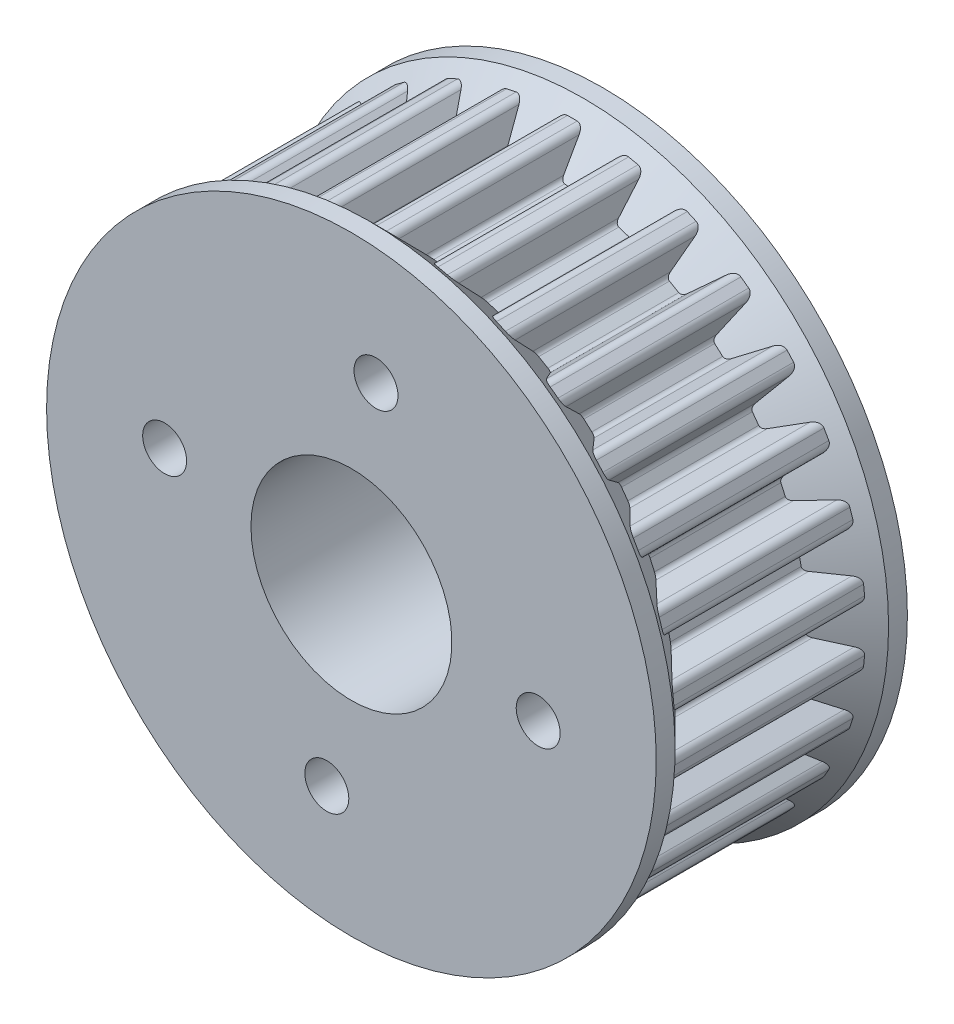
SolidWorks part; units mm, degrees
ref_plane "Plan de face" through (0, 0, 0) normal (0, 0, 1) x (1, 0, 0)
ref_plane "Plan de dessus" through (0, 0, 0) normal (0, 1, 0) x (1, 0, 0)
ref_plane "Plan de droite" through (0, 0, 0) normal (1, 0, 0) x (0, 0, -1)
sketch "Esquisse1" plane through (0, 0, 0) normal (0, 0, 1) x (1, 0, 0)
  line L0 (0, 0) -> (0, 23.875) construction
  line L1 (0, 0) -> (4.9639, 23.3533) construction
  line L2 (0, 0) -> (2.4956, 23.7442) construction
  line L3 (0.3858, 23.3597) -> (0, 23.3597)
  line L4 (0.9653, 22.915) -> (1.4252, 21.1988)
  line L5 (1.7697, 20.9045) -> (2.6152, 20.8157)
  line L6 (3.8201, 22.6149) -> (3.0135, 21.0319)
  line L7 (4.4794, 22.9294) -> (4.8568, 22.8492)
  line L8 (5.2341, 22.769) -> (4.8568, 22.8492)
  line L9 (5.7085, 22.2135) -> (5.8015, 20.4393)
  line L10 (6.0773, 20.0798) -> (6.8859, 19.8171)
  line L11 (8.4385, 21.3265) -> (7.3204, 19.9457)
  line L12 (9.1488, 21.497) -> (9.5012, 21.3401)
  line L13 (9.8537, 21.1832) -> (9.5012, 21.3401)
  line L14 (10.2022, 20.5412) -> (9.9243, 18.7864)
  line L15 (10.1194, 18.3774) -> (10.8556, 17.9523)
  line L16 (12.6881, 19.106) -> (11.3074, 17.9879)
  line L17 (13.4184, 19.1251) -> (13.7305, 18.8984)
  line L18 (14.0426, 18.6716) -> (13.7305, 18.8984)
  line L19 (14.25, 17.9712) -> (13.6133, 16.3125)
  line L20 (13.7191, 15.8719) -> (14.3509, 15.303)
  line L21 (16.3832, 16.0505) -> (14.8002, 15.2439)
  line L22 (17.1015, 15.9174) -> (17.3596, 15.6307)
  line L23 (17.6178, 15.344) -> (17.3596, 15.6307)
  line L24 (17.6751, 14.6157) -> (16.7074, 13.1257)
  line L25 (16.7193, 12.6727) -> (17.219, 11.9849)
  line L26 (19.3623, 12.2935) -> (17.6461, 11.8336)
  line L27 (20.0372, 12.0139) -> (20.2301, 11.6798)
  line L28 (20.423, 11.3458) -> (20.2301, 11.6798)
  line L29 (20.3276, 10.6215) -> (19.0713, 9.3652)
  line L30 (18.9887, 8.9196) -> (19.3345, 8.143)
  line L31 (21.4951, 7.9992) -> (19.7209, 7.9062)
  line L32 (22.0972, 7.5854) -> (22.2164, 7.2185)
  line L33 (22.3356, 6.8517) -> (22.2164, 7.2185)
  line L34 (22.0917, 6.163) -> (20.6017, 5.1954)
  line L35 (20.4283, 4.7767) -> (20.605, 3.9451)
  line L36 (22.6885, 3.3553) -> (20.9337, 3.6332)
  line L37 (23.1914, 2.8254) -> (23.2317, 2.4418)
  line L38 (23.272, 2.0581) -> (23.2317, 2.4418)
  line L39 (22.8903, 1.4352) -> (21.2317, 0.7985)
  line L40 (20.975, 0.4251) -> (20.975, -0.4251)
  line L41 (22.8903, -1.4352) -> (21.2317, -0.7985)
  line L42 (23.272, -2.0581) -> (23.2317, -2.4418)
  line L43 (23.1914, -2.8254) -> (23.2317, -2.4418)
  line L44 (22.6885, -3.3553) -> (20.9337, -3.6332)
  line L45 (20.605, -3.9451) -> (20.4283, -4.7767)
  line L46 (22.0917, -6.163) -> (20.6017, -5.1954)
  line L47 (22.3356, -6.8517) -> (22.2164, -7.2185)
  line L48 (22.0972, -7.5854) -> (22.2164, -7.2185)
  line L49 (21.4951, -7.9992) -> (19.7209, -7.9062)
  line L50 (19.3345, -8.143) -> (18.9887, -8.9196)
  line L51 (20.3276, -10.6215) -> (19.0713, -9.3652)
  line L52 (20.423, -11.3458) -> (20.2301, -11.6798)
  line L53 (20.0372, -12.0139) -> (20.2301, -11.6798)
  line L54 (19.3623, -12.2935) -> (17.6461, -11.8336)
  line L55 (17.219, -11.9849) -> (16.7193, -12.6727)
  line L56 (17.6751, -14.6157) -> (16.7074, -13.1257)
  line L57 (17.6178, -15.344) -> (17.3596, -15.6307)
  line L58 (17.1015, -15.9174) -> (17.3596, -15.6307)
  line L59 (16.3832, -16.0505) -> (14.8002, -15.2439)
  line L60 (14.3509, -15.303) -> (13.7191, -15.8719)
  line L61 (14.25, -17.9712) -> (13.6133, -16.3125)
  line L62 (14.0426, -18.6716) -> (13.7305, -18.8984)
  line L63 (13.4184, -19.1251) -> (13.7305, -18.8984)
  line L64 (12.6881, -19.106) -> (11.3074, -17.9879)
  line L65 (10.8556, -17.9523) -> (10.1194, -18.3774)
  line L66 (10.2022, -20.5412) -> (9.9243, -18.7864)
  line L67 (9.8537, -21.1832) -> (9.5012, -21.3401)
  line L68 (9.1488, -21.497) -> (9.5012, -21.3401)
  line L69 (8.4385, -21.3265) -> (7.3204, -19.9457)
  line L70 (6.8859, -19.8171) -> (6.0773, -20.0798)
  line L71 (5.7085, -22.2135) -> (5.8015, -20.4393)
  line L72 (5.2341, -22.769) -> (4.8568, -22.8492)
  line L73 (4.4794, -22.9294) -> (4.8568, -22.8492)
  line L74 (3.8201, -22.6149) -> (3.0135, -21.0319)
  line L75 (2.6152, -20.8157) -> (1.7697, -20.9045)
  line L76 (0.9653, -22.915) -> (1.4252, -21.1988)
  line L77 (0.3858, -23.3597) -> (0, -23.3597)
  line L78 (-0.3858, -23.3597) -> (0, -23.3597)
  line L79 (-0.9653, -22.915) -> (-1.4252, -21.1988)
  line L80 (-1.7697, -20.9045) -> (-2.6152, -20.8157)
  line L81 (-3.8201, -22.6149) -> (-3.0135, -21.0319)
  line L82 (-4.4794, -22.9294) -> (-4.8568, -22.8492)
  line L83 (-5.2341, -22.769) -> (-4.8568, -22.8492)
  line L84 (-5.7085, -22.2135) -> (-5.8015, -20.4393)
  line L85 (-6.0773, -20.0798) -> (-6.8859, -19.8171)
  line L86 (-8.4385, -21.3265) -> (-7.3204, -19.9457)
  line L87 (-9.1488, -21.497) -> (-9.5012, -21.3401)
  line L88 (-9.8537, -21.1832) -> (-9.5012, -21.3401)
  line L89 (-10.2022, -20.5412) -> (-9.9243, -18.7864)
  line L90 (-10.1194, -18.3774) -> (-10.8556, -17.9523)
  line L91 (-12.6881, -19.106) -> (-11.3074, -17.9879)
  line L92 (-13.4184, -19.1251) -> (-13.7305, -18.8984)
  line L93 (-14.0426, -18.6716) -> (-13.7305, -18.8984)
  line L94 (-14.25, -17.9712) -> (-13.6133, -16.3125)
  line L95 (-13.7191, -15.8719) -> (-14.3509, -15.303)
  line L96 (-16.3832, -16.0505) -> (-14.8002, -15.2439)
  line L97 (-17.1015, -15.9174) -> (-17.3596, -15.6307)
  line L98 (-17.6178, -15.344) -> (-17.3596, -15.6307)
  line L99 (-17.6751, -14.6157) -> (-16.7074, -13.1257)
  line L100 (-16.7193, -12.6727) -> (-17.219, -11.9849)
  line L101 (-19.3623, -12.2935) -> (-17.6461, -11.8336)
  line L102 (-20.0372, -12.0139) -> (-20.2301, -11.6798)
  line L103 (-20.423, -11.3458) -> (-20.2301, -11.6798)
  line L104 (-20.3276, -10.6215) -> (-19.0713, -9.3652)
  line L105 (-18.9887, -8.9196) -> (-19.3345, -8.143)
  line L106 (-21.4951, -7.9992) -> (-19.7209, -7.9062)
  line L107 (-22.0972, -7.5854) -> (-22.2164, -7.2185)
  line L108 (-22.3356, -6.8517) -> (-22.2164, -7.2185)
  line L109 (-22.0917, -6.163) -> (-20.6017, -5.1954)
  line L110 (-20.4283, -4.7767) -> (-20.605, -3.9451)
  line L111 (-22.6885, -3.3553) -> (-20.9337, -3.6332)
  line L112 (-23.1914, -2.8254) -> (-23.2317, -2.4418)
  line L113 (-23.272, -2.0581) -> (-23.2317, -2.4418)
  line L114 (-22.8903, -1.4352) -> (-21.2317, -0.7985)
  line L115 (-20.975, -0.4251) -> (-20.975, 0.4251)
  line L116 (-22.8903, 1.4352) -> (-21.2317, 0.7985)
  line L117 (-23.272, 2.0581) -> (-23.2317, 2.4418)
  line L118 (-23.1914, 2.8254) -> (-23.2317, 2.4418)
  line L119 (-22.6885, 3.3553) -> (-20.9337, 3.6332)
  line L120 (-20.605, 3.9451) -> (-20.4283, 4.7767)
  line L121 (-22.0917, 6.163) -> (-20.6017, 5.1954)
  line L122 (-22.3356, 6.8517) -> (-22.2164, 7.2185)
  line L123 (-22.0972, 7.5854) -> (-22.2164, 7.2185)
  line L124 (-21.4951, 7.9992) -> (-19.7209, 7.9062)
  line L125 (-19.3345, 8.143) -> (-18.9887, 8.9196)
  line L126 (-20.3276, 10.6215) -> (-19.0713, 9.3652)
  line L127 (-20.423, 11.3458) -> (-20.2301, 11.6798)
  line L128 (-20.0372, 12.0139) -> (-20.2301, 11.6798)
  line L129 (-19.3623, 12.2935) -> (-17.6461, 11.8336)
  line L130 (-17.219, 11.9849) -> (-16.7193, 12.6727)
  line L131 (-17.6751, 14.6157) -> (-16.7074, 13.1257)
  line L132 (-17.6178, 15.344) -> (-17.3596, 15.6307)
  line L133 (-17.1015, 15.9174) -> (-17.3596, 15.6307)
  line L134 (-16.3832, 16.0505) -> (-14.8002, 15.2439)
  line L135 (-14.3509, 15.303) -> (-13.7191, 15.8719)
  line L136 (-14.25, 17.9712) -> (-13.6133, 16.3125)
  line L137 (-14.0426, 18.6716) -> (-13.7305, 18.8984)
  line L138 (-13.4184, 19.1251) -> (-13.7305, 18.8984)
  line L139 (-12.6881, 19.106) -> (-11.3074, 17.9879)
  line L140 (-10.8556, 17.9523) -> (-10.1194, 18.3774)
  line L141 (-10.2022, 20.5412) -> (-9.9243, 18.7864)
  line L142 (-9.8537, 21.1832) -> (-9.5012, 21.3401)
  line L143 (-9.1488, 21.497) -> (-9.5012, 21.3401)
  line L144 (-8.4385, 21.3265) -> (-7.3204, 19.9457)
  line L145 (-6.8859, 19.8171) -> (-6.0773, 20.0798)
  line L146 (-5.7085, 22.2135) -> (-5.8015, 20.4393)
  line L147 (-5.2341, 22.769) -> (-4.8568, 22.8492)
  line L148 (-4.4794, 22.9294) -> (-4.8568, 22.8492)
  line L149 (-3.8201, 22.6149) -> (-3.0135, 21.0319)
  line L150 (-2.6152, 20.8157) -> (-1.7697, 20.9045)
  line L151 (-0.9653, 22.915) -> (-1.4252, 21.1988)
  line L152 (-0.3858, 23.3597) -> (0, 23.3597)
  circle A0 centre (0, 0) radius 23.875 construction
  circle A1 centre (0, 0) radius 23.375 construction
  circle A2 centre (0, 0) radius 20.975 construction
  arc A3 (4.4794, 22.9294) -> (3.8201, 22.6149) centre (4.3547, 22.3425) ccw
  arc A4 (0.9653, 22.915) -> (0.3858, 23.3597) centre (0.3858, 22.7597) ccw
  arc A5 (9.1488, 21.497) -> (8.4385, 21.3265) centre (8.9048, 20.9489) ccw
  arc A6 (5.7085, 22.2135) -> (5.2341, 22.769) centre (5.1093, 22.1821) ccw
  arc A7 (7.3204, 19.9457) -> (6.8859, 19.8171) centre (7.0095, 20.1975) cw
  arc A8 (6.0773, 20.0798) -> (5.8015, 20.4393) centre (6.201, 20.4602) cw
  arc A9 (13.4184, 19.1251) -> (12.6881, 19.106) centre (13.0657, 18.6397) ccw
  arc A10 (10.2022, 20.5412) -> (9.8537, 21.1832) centre (9.6096, 20.6351) ccw
  arc A11 (11.3074, 17.9879) -> (10.8556, 17.9523) centre (11.0556, 18.2987) cw
  arc A12 (10.1194, 18.3774) -> (9.9243, 18.7864) centre (10.3194, 18.7238) cw
  arc A13 (17.1015, 15.9174) -> (16.3832, 16.0505) centre (16.6556, 15.5159) ccw
  arc A14 (14.25, 17.9712) -> (14.0426, 18.6716) centre (13.6899, 18.1862) ccw
  arc A15 (14.8002, 15.2439) -> (14.3509, 15.303) centre (14.6186, 15.6003) cw
  arc A16 (13.7191, 15.8719) -> (13.6133, 16.3125) centre (13.9868, 16.1692) cw
  arc A17 (20.0372, 12.0139) -> (19.3623, 12.2935) centre (19.5176, 11.7139) ccw
  arc A18 (17.6751, 14.6157) -> (17.6178, 15.344) centre (17.1719, 14.9425) ccw
  arc A19 (17.6461, 11.8336) -> (17.219, 11.9849) centre (17.5426, 12.22) cw
  arc A20 (16.7193, 12.6727) -> (16.7074, 13.1257) centre (17.0429, 12.9078) cw
  arc A21 (22.0972, 7.5854) -> (21.4951, 7.9992) centre (21.5265, 7.4) ccw
  arc A22 (20.3276, 10.6215) -> (20.423, 11.3458) centre (19.9033, 11.0458) ccw
  arc A23 (19.7209, 7.9062) -> (19.3345, 8.143) centre (19.6999, 8.3057) cw
  arc A24 (18.9887, 8.9196) -> (19.0713, 9.3652) centre (19.3541, 9.0823) cw
  arc A25 (23.1914, 2.8254) -> (22.6885, 3.3553) centre (22.5947, 2.7627) ccw
  arc A26 (22.0917, 6.163) -> (22.3356, 6.8517) centre (21.765, 6.6662) ccw
  arc A27 (20.9337, 3.6332) -> (20.605, 3.9451) centre (20.9963, 4.0283) cw
  arc A28 (20.4283, 4.7767) -> (20.6017, 5.1954) centre (20.8195, 4.8599) cw
  arc A29 (23.272, -2.0581) -> (22.8903, -1.4352) centre (22.6753, -1.9954) ccw
  arc A30 (22.8903, 1.4352) -> (23.272, 2.0581) centre (22.6753, 1.9954) ccw
  arc A31 (21.2317, -0.7985) -> (20.975, -0.4251) centre (21.375, -0.4251) cw
  arc A32 (20.975, 0.4251) -> (21.2317, 0.7985) centre (21.375, 0.4251) cw
  arc A33 (22.3356, -6.8517) -> (22.0917, -6.163) centre (21.765, -6.6662) ccw
  arc A34 (22.6885, -3.3553) -> (23.1914, -2.8254) centre (22.5947, -2.7627) ccw
  arc A35 (20.6017, -5.1954) -> (20.4283, -4.7767) centre (20.8195, -4.8599) cw
  arc A36 (20.605, -3.9451) -> (20.9337, -3.6332) centre (20.9963, -4.0283) cw
  arc A37 (20.423, -11.3458) -> (20.3276, -10.6215) centre (19.9033, -11.0458) ccw
  arc A38 (21.4951, -7.9992) -> (22.0972, -7.5854) centre (21.5265, -7.4) ccw
  arc A39 (19.0713, -9.3652) -> (18.9887, -8.9196) centre (19.3541, -9.0823) cw
  arc A40 (19.3345, -8.143) -> (19.7209, -7.9062) centre (19.6999, -8.3057) cw
  arc A41 (17.6178, -15.344) -> (17.6751, -14.6157) centre (17.1719, -14.9425) ccw
  arc A42 (19.3623, -12.2935) -> (20.0372, -12.0139) centre (19.5176, -11.7139) ccw
  arc A43 (16.7074, -13.1257) -> (16.7193, -12.6727) centre (17.0429, -12.9078) cw
  arc A44 (17.219, -11.9849) -> (17.6461, -11.8336) centre (17.5426, -12.22) cw
  arc A45 (14.0426, -18.6716) -> (14.25, -17.9712) centre (13.6899, -18.1862) ccw
  arc A46 (16.3832, -16.0505) -> (17.1015, -15.9174) centre (16.6556, -15.5159) ccw
  arc A47 (13.6133, -16.3125) -> (13.7191, -15.8719) centre (13.9868, -16.1692) cw
  arc A48 (14.3509, -15.303) -> (14.8002, -15.2439) centre (14.6186, -15.6003) cw
  arc A49 (9.8537, -21.1832) -> (10.2022, -20.5412) centre (9.6096, -20.6351) ccw
  arc A50 (12.6881, -19.106) -> (13.4184, -19.1251) centre (13.0657, -18.6397) ccw
  arc A51 (9.9243, -18.7864) -> (10.1194, -18.3774) centre (10.3194, -18.7238) cw
  arc A52 (10.8556, -17.9523) -> (11.3074, -17.9879) centre (11.0556, -18.2987) cw
  arc A53 (5.2341, -22.769) -> (5.7085, -22.2135) centre (5.1093, -22.1821) ccw
  arc A54 (8.4385, -21.3265) -> (9.1488, -21.497) centre (8.9048, -20.9489) ccw
  arc A55 (5.8015, -20.4393) -> (6.0773, -20.0798) centre (6.201, -20.4602) cw
  arc A56 (6.8859, -19.8171) -> (7.3204, -19.9457) centre (7.0095, -20.1975) cw
  arc A57 (0.3858, -23.3597) -> (0.9653, -22.915) centre (0.3858, -22.7597) ccw
  arc A58 (3.8201, -22.6149) -> (4.4794, -22.9294) centre (4.3547, -22.3425) ccw
  arc A59 (1.4252, -21.1988) -> (1.7697, -20.9045) centre (1.8115, -21.3023) cw
  arc A60 (2.6152, -20.8157) -> (3.0135, -21.0319) centre (2.6571, -21.2135) cw
  arc A61 (-4.4794, -22.9294) -> (-3.8201, -22.6149) centre (-4.3547, -22.3425) ccw
  arc A62 (-0.9653, -22.915) -> (-0.3858, -23.3597) centre (-0.3858, -22.7597) ccw
  arc A63 (3.0135, 21.0319) -> (2.6152, 20.8157) centre (2.6571, 21.2135) cw
  arc A64 (1.7697, 20.9045) -> (1.4252, 21.1988) centre (1.8115, 21.3023) cw
  arc A65 (-3.0135, -21.0319) -> (-2.6152, -20.8157) centre (-2.6571, -21.2135) cw
  arc A66 (-1.7697, -20.9045) -> (-1.4252, -21.1988) centre (-1.8115, -21.3023) cw
  arc A67 (-9.1488, -21.497) -> (-8.4385, -21.3265) centre (-8.9048, -20.9489) ccw
  arc A68 (-5.7085, -22.2135) -> (-5.2341, -22.769) centre (-5.1093, -22.1821) ccw
  arc A69 (-7.3204, -19.9457) -> (-6.8859, -19.8171) centre (-7.0095, -20.1975) cw
  arc A70 (-6.0773, -20.0798) -> (-5.8015, -20.4393) centre (-6.201, -20.4602) cw
  arc A71 (-13.4184, -19.1251) -> (-12.6881, -19.106) centre (-13.0657, -18.6397) ccw
  arc A72 (-10.2022, -20.5412) -> (-9.8537, -21.1832) centre (-9.6096, -20.6351) ccw
  arc A73 (-11.3074, -17.9879) -> (-10.8556, -17.9523) centre (-11.0556, -18.2987) cw
  arc A74 (-10.1194, -18.3774) -> (-9.9243, -18.7864) centre (-10.3194, -18.7238) cw
  arc A75 (-17.1015, -15.9174) -> (-16.3832, -16.0505) centre (-16.6556, -15.5159) ccw
  arc A76 (-14.25, -17.9712) -> (-14.0426, -18.6716) centre (-13.6899, -18.1862) ccw
  arc A77 (-14.8002, -15.2439) -> (-14.3509, -15.303) centre (-14.6186, -15.6003) cw
  arc A78 (-13.7191, -15.8719) -> (-13.6133, -16.3125) centre (-13.9868, -16.1692) cw
  arc A79 (-20.0372, -12.0139) -> (-19.3623, -12.2935) centre (-19.5176, -11.7139) ccw
  arc A80 (-17.6751, -14.6157) -> (-17.6178, -15.344) centre (-17.1719, -14.9425) ccw
  arc A81 (-17.6461, -11.8336) -> (-17.219, -11.9849) centre (-17.5426, -12.22) cw
  arc A82 (-16.7193, -12.6727) -> (-16.7074, -13.1257) centre (-17.0429, -12.9078) cw
  arc A83 (-22.0972, -7.5854) -> (-21.4951, -7.9992) centre (-21.5265, -7.4) ccw
  arc A84 (-20.3276, -10.6215) -> (-20.423, -11.3458) centre (-19.9033, -11.0458) ccw
  arc A85 (-19.7209, -7.9062) -> (-19.3345, -8.143) centre (-19.6999, -8.3057) cw
  arc A86 (-18.9887, -8.9196) -> (-19.0713, -9.3652) centre (-19.3541, -9.0823) cw
  arc A87 (-23.1914, -2.8254) -> (-22.6885, -3.3553) centre (-22.5947, -2.7627) ccw
  arc A88 (-22.0917, -6.163) -> (-22.3356, -6.8517) centre (-21.765, -6.6662) ccw
  arc A89 (-20.9337, -3.6332) -> (-20.605, -3.9451) centre (-20.9963, -4.0283) cw
  arc A90 (-20.4283, -4.7767) -> (-20.6017, -5.1954) centre (-20.8195, -4.8599) cw
  arc A91 (-23.272, 2.0581) -> (-22.8903, 1.4352) centre (-22.6753, 1.9954) ccw
  arc A92 (-22.8903, -1.4352) -> (-23.272, -2.0581) centre (-22.6753, -1.9954) ccw
  arc A93 (-21.2317, 0.7985) -> (-20.975, 0.4251) centre (-21.375, 0.4251) cw
  arc A94 (-20.975, -0.4251) -> (-21.2317, -0.7985) centre (-21.375, -0.4251) cw
  arc A95 (-22.3356, 6.8517) -> (-22.0917, 6.163) centre (-21.765, 6.6662) ccw
  arc A96 (-22.6885, 3.3553) -> (-23.1914, 2.8254) centre (-22.5947, 2.7627) ccw
  arc A97 (-20.6017, 5.1954) -> (-20.4283, 4.7767) centre (-20.8195, 4.8599) cw
  arc A98 (-20.605, 3.9451) -> (-20.9337, 3.6332) centre (-20.9963, 4.0283) cw
  arc A99 (-20.423, 11.3458) -> (-20.3276, 10.6215) centre (-19.9033, 11.0458) ccw
  arc A100 (-21.4951, 7.9992) -> (-22.0972, 7.5854) centre (-21.5265, 7.4) ccw
  arc A101 (-19.0713, 9.3652) -> (-18.9887, 8.9196) centre (-19.3541, 9.0823) cw
  arc A102 (-19.3345, 8.143) -> (-19.7209, 7.9062) centre (-19.6999, 8.3057) cw
  arc A103 (-17.6178, 15.344) -> (-17.6751, 14.6157) centre (-17.1719, 14.9425) ccw
  arc A104 (-19.3623, 12.2935) -> (-20.0372, 12.0139) centre (-19.5176, 11.7139) ccw
  arc A105 (-16.7074, 13.1257) -> (-16.7193, 12.6727) centre (-17.0429, 12.9078) cw
  arc A106 (-17.219, 11.9849) -> (-17.6461, 11.8336) centre (-17.5426, 12.22) cw
  arc A107 (-14.0426, 18.6716) -> (-14.25, 17.9712) centre (-13.6899, 18.1862) ccw
  arc A108 (-16.3832, 16.0505) -> (-17.1015, 15.9174) centre (-16.6556, 15.5159) ccw
  arc A109 (-13.6133, 16.3125) -> (-13.7191, 15.8719) centre (-13.9868, 16.1692) cw
  arc A110 (-14.3509, 15.303) -> (-14.8002, 15.2439) centre (-14.6186, 15.6003) cw
  arc A111 (-9.8537, 21.1832) -> (-10.2022, 20.5412) centre (-9.6096, 20.6351) ccw
  arc A112 (-12.6881, 19.106) -> (-13.4184, 19.1251) centre (-13.0657, 18.6397) ccw
  arc A113 (-9.9243, 18.7864) -> (-10.1194, 18.3774) centre (-10.3194, 18.7238) cw
  arc A114 (-10.8556, 17.9523) -> (-11.3074, 17.9879) centre (-11.0556, 18.2987) cw
  arc A115 (-5.2341, 22.769) -> (-5.7085, 22.2135) centre (-5.1093, 22.1821) ccw
  arc A116 (-8.4385, 21.3265) -> (-9.1488, 21.497) centre (-8.9048, 20.9489) ccw
  arc A117 (-5.8015, 20.4393) -> (-6.0773, 20.0798) centre (-6.201, 20.4602) cw
  arc A118 (-6.8859, 19.8171) -> (-7.3204, 19.9457) centre (-7.0095, 20.1975) cw
  arc A119 (-0.3858, 23.3597) -> (-0.9653, 22.915) centre (-0.3858, 22.7597) ccw
  arc A120 (-3.8201, 22.6149) -> (-4.4794, 22.9294) centre (-4.3547, 22.3425) ccw
  arc A121 (-1.4252, 21.1988) -> (-1.7697, 20.9045) centre (-1.8115, 21.3023) cw
  arc A122 (-2.6152, 20.8157) -> (-3.0135, 21.0319) centre (-2.6571, 21.2135) cw
  point P14 (2.1925, 20.8601)
  point P16 (4.0291, 23.0251)
  point P20 (0.8462, 23.3597)
  point P31 (2.8886, 20.7869)
  point P32 (6.4816, 19.9484)
  point P48 (10.4875, 18.1649)
  point P64 (1.4963, 20.9333)
  point P65 (14.035, 15.5875)
  point P80 (16.9691, 12.3288)
  point P95 (19.1616, 8.5313)
  point P110 (20.5166, 4.3609)
  point P125 (20.975, 0)
  point P140 (20.5166, -4.3609)
  point P155 (19.1616, -8.5313)
  point P170 (16.9691, -12.3288)
  point P185 (14.035, -15.5875)
  point P200 (10.4875, -18.1649)
  point P215 (6.4816, -19.9484)
  point P230 (2.1925, -20.8601)
  point P245 (-2.1925, -20.8601)
  point P260 (-6.4816, -19.9484)
  point P275 (-10.4875, -18.1649)
  point P290 (-14.035, -15.5875)
  point P305 (-16.9691, -12.3288)
  point P320 (-19.1616, -8.5313)
  point P335 (-20.5166, -4.3609)
  point P350 (-20.975, 0)
  point P365 (-20.5166, 4.3609)
  point P380 (-19.1616, 8.5313)
  point P395 (-16.9691, 12.3288)
  point P410 (-14.035, 15.5875)
  point P425 (-10.4875, 18.1649)
  point P440 (-6.4816, 19.9484)
  point P455 (-2.1925, 20.8601)
  point P464 (0, 0)
  dimension "D1" = 47.75
  dimension "D2" = 0.5
  dimension "D5" = 2.4
  dimension "D8" = 0.6
  dimension "D10" = 3.2004
  dimension "D12" = 0.4
  dimension "D3" = 12
  dimension "D4" = 6
  dimension "D6" = 15
  dimension "D7" = 1.4
  dimension "D9" = 1.6923
  dimension "D11" = 30
extrude "Boss.-Extru.1" add sketch "Esquisse1" along normal blind 19
sketch "Esquisse3" plane through (0, 0, 0) normal (0, 1, 0) x (1, 0, 0)
  line L0 (-20.772, -4.5) -> (-20.772, -14.5)
  line L1 (-20.772, -14.5) -> (-24.272, -18)
  line L2 (-24.272, -18) -> (-24.272, -19.5)
  line L3 (-24.272, -19.5) -> (-8, -19.5)
  line L4 (-8, -19.5) -> (-8, 0.5)
  line L5 (-8, 0.5) -> (-24.272, 0.5)
  line L6 (-24.272, 0.5) -> (-24.272, -1)
  line L7 (-24.272, -1) -> (-20.772, -4.5)
  line L9 (0, 0) -> (0, -19) construction
  line L10 (0.3858, -19) -> (-0.3858, -19) construction
  line L11 (0, -9.5) -> (-20.772, -9.5) construction
  line L13 (-23.272, -19) -> (-23.272, 0) construction
  point P2 (-24.527, 0.9494)
  point P9 (-25.2802, 0.5)
  dimension "D1" = 10
  dimension "D2" = 20
  dimension "D3" = 2.5
  dimension "D4" = 1.5
  dimension "D5" = 1.5
  dimension "D6" = 45
  dimension "D7" = 45
  dimension "D8" = 16
revolve "Révolution1" add sketch "Esquisse3" angle 360 about L9
sketch "Esquisse2" plane through (0, 0, -0.5) normal (0, 0, 1) x (1, 0, 0)
  line L0 (0, 0) -> (1.9579, 14.8717) construction
  line L1 (0, 0) -> (0, 15) construction
  circle A0 centre (0, 0) radius 15 construction
  circle A1 centre (14.8717, -1.9579) radius 1.75
  circle A3 centre (1.9579, 14.8717) radius 1.75
  circle A4 centre (-1.9579, -14.8717) radius 1.75
  circle A5 centre (-14.8717, 1.9579) radius 1.75
  point P15 (0, 0)
  point P19 (0, 0)
  dimension "D1" = 30
  dimension "D2" = 7.5
  dimension "D5" = 3.5
  dimension "D4" = 4
extrude "Enlèv. mat.-Extru.1" cut sketch "Esquisse2" along normal through all
sketch "Esquisse4" plane through (0, 0, -0.5) normal (0, 0, -1) x (-1, 0, 0)
  circle A1 centre (0, 0) radius 9
  dimension "D1" = 18
extrude "Enlèv. mat.-Extru.2" cut sketch "Esquisse4" against normal blind 4
sketch "Esquisse5" plane through (0, 0, 3.5) normal (0, 0, -1) x (-1, 0, 0)
  circle A0 centre (0, 0) radius 8
  dimension "D1" = 16
extrude "Enlèv. mat.-Extru.3" cut sketch "Esquisse5" against normal through all
sketch "Esquisse6" plane through (0, 0, -0.5) normal (0, 0, -1) x (-1, 0, 0)
  circle A0 centre (-1.9579, 14.8717) radius 1.75 construction
  circle A1 centre (-14.8717, -1.9579) radius 1.75 construction
  circle A2 centre (1.9579, -14.8717) radius 1.75 construction
  circle A3 centre (14.8717, 1.9579) radius 1.75 construction
  circle A12 centre (-1.9579, 14.8717) radius 1.75
  circle A13 centre (-14.8717, -1.9579) radius 1.75
  circle A14 centre (1.9579, -14.8717) radius 1.75
  circle A15 centre (14.8717, 1.9579) radius 1.75
  circle A16 centre (-1.9579, 14.8717) radius 3.75
  circle A17 centre (-14.8717, -1.9579) radius 3.75
  circle A18 centre (1.9579, -14.8717) radius 3.75
  circle A19 centre (14.8717, 1.9579) radius 3.75
  dimension "D1" = 2
extrude "Enlèv. mat.-Extru.4" cut sketch "Esquisse6" against normal blind 4
